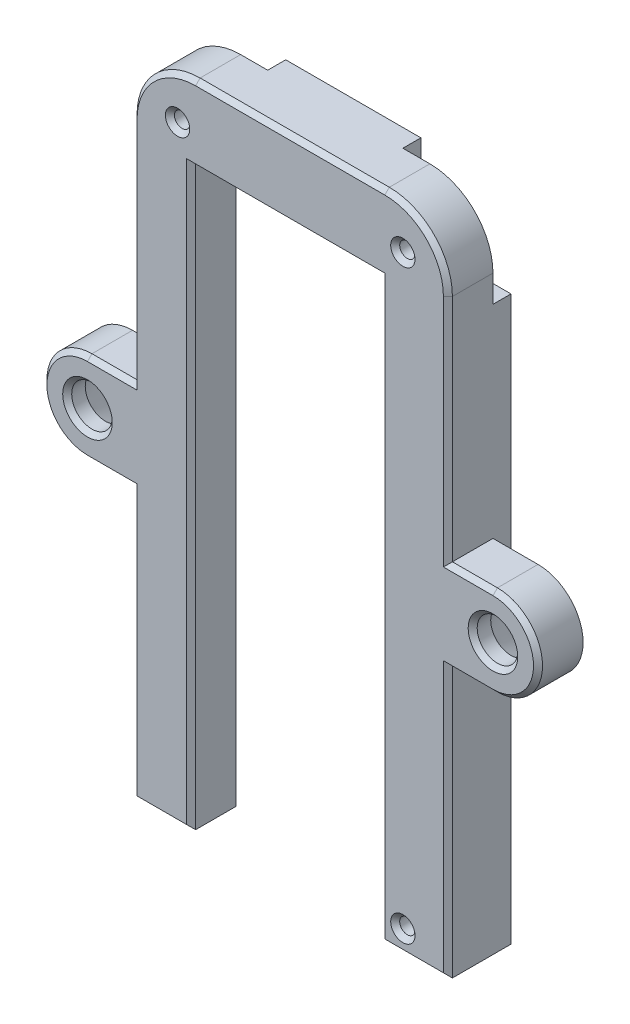
SolidWorks part; units mm, degrees
ref_plane "Front Plane" through (0, 0, 0) normal (0, 0, 1) x (1, 0, 0)
ref_plane "Top Plane" through (0, 0, 0) normal (0, 1, 0) x (1, 0, 0)
ref_plane "Right Plane" through (0, 0, 0) normal (1, 0, 0) x (0, 0, -1)
sketch "Sketch1" plane through (0, 0, 0) normal (0, 0, 1) x (1, 0, 0)
  line L0 (-11, -35) -> (-11, 29)
  line L1 (-15, -35) -> (15, -35) construction
  line L2 (-15, -35) -> (-15, 35) construction
  line L3 (-15, 35) -> (15, 35) construction
  line L4 (15, -35) -> (15, 35) construction
  line L5 (-11, 29) -> (10, 29)
  line L6 (10, 29) -> (10, -35)
  line L7 (-11, -35) -> (-17.5, -35)
  line L8 (-17.5, -35) -> (-17.5, 37.5)
  line L9 (-17.5, 37.5) -> (17.5, 37.5)
  line L10 (17.5, 37.5) -> (17.5, -35)
  line L11 (17.5, -35) -> (10, -35)
  circle A0 centre (-12.5, 32.5) radius 0.85
  circle A1 centre (12.5, 32.5) radius 0.85
  circle A3 centre (12.5, -32.5) radius 0.85
  point P4 (0, 35)
  point P5 (-15, 0)
  point P21 (0, 0)
  point P22 (0, 0)
  point P23 (0, 0)
  point P26 (0, 0)
  point P27 (0, 0)
  point P28 (0, 0)
  point P29 (0, 0)
  dimension "D6" = 1.7
  dimension "D1" = 30
  dimension "D2" = 70
  dimension "D3" = 4
  dimension "D4" = 5
  dimension "D5" = 6
  dimension "D7" = 2.5
  dimension "D8" = 2.5
  dimension "D9" = 2.5
  dimension "D10" = 2.5
  dimension "D11" = 6.5
  dimension "D12" = 7.5
  dimension "D13" = 8.5
  dimension "D16" = 2.5
extrude "Boss-Extrude1" add sketch "Sketch1" along normal blind 5
sketch "Sketch2" plane through (0, 0, 0) normal (0, 0, 1) x (1, 0, 0)
  line L0 (17.5, -35) -> (10, -35) construction
  line L1 (17.5, 37.5) -> (30, 37.5)
  line L2 (17.5, 37.5) -> (17.5, -35)
  line L3 (17.5, -35) -> (15.1, -35)
  line L4 (15.1, 35.1) -> (15.1, -35)
  line L5 (-17.5, 37.5) -> (-30, 37.5)
  line L6 (-17.5, 37.5) -> (-17.5, -35)
  line L7 (-17.5, -35) -> (-15.1, -35)
  line L8 (-15.1, 35.1) -> (-15.1, -35)
  line L9 (30, 37.5) -> (-30, 37.5)
  line L11 (15.1, 35.1) -> (-15.1, 35.1)
  line L12 (15, -35) -> (15, 35) construction
  line L13 (-17.5, -35) -> (-11, -35) construction
  line L15 (-15, -35) -> (-15, 35) construction
  line L16 (-15, 35) -> (15, 35) construction
  dimension "D1" = 0.1
  dimension "D2" = 0.1
  dimension "D3" = 0.1
extrude "Boss-Extrude2" add sketch "Sketch2" against normal blind 2 contours L11 L4 L3 L2 L9 L6 L7 L8 region at (16.6949, 1.25, 0)
sketch "Sketch3" plane through (0, 0, 0) normal (0, 0, 1) x (1, 0, 0)
  line L0 (17.5, 37.5) -> (17.5, -35) construction
  line L1 (22.5, 5) -> (17.5, 5)
  line L3 (22.5, -5) -> (17.5, -5)
  line L4 (17.5, 5) -> (17.5, -5)
  line L5 (-17.5, -35) -> (-17.5, 37.5) construction
  line L6 (-22.5, 5) -> (-17.5, 5)
  line L8 (-22.5, -5) -> (-17.5, -5)
  line L9 (-17.5, 5) -> (-17.5, -5)
  arc A0 (22.5, -5) -> (22.5, 5) centre (22.5, 0) ccw
  arc A1 (-22.5, 5) -> (-22.5, -5) centre (-22.5, 0) ccw
  circle A2 centre (22.5, 0) radius 2.25
  circle A3 centre (-22.5, 0) radius 2.25
  dimension "D1" = 10
  dimension "D2" = 10
  dimension "D3" = 4.5
  dimension "D4" = 4.5
extrude "Boss-Extrude3" add sketch "Sketch3" along normal up to surface (5 mm away) up to face at (-0.25, -0.875, 5)
sketch "Sketch4" plane through (0, 0, 0) normal (0, 0, -1) x (-1, 0, 0)
  circle A0 centre (-22.5, 0) radius 3.5
  circle A1 centre (22.5, 0) radius 3.5
  dimension "D1" = 7
  dimension "D2" = 7
extrude "Cut-Extrude1" cut sketch "Sketch4" against normal blind 3
sketch "Sketch5" plane through (0, 0, 0) normal (0, 0, -1) x (-1, 0, 0)
  line L1 (-7.5, 37.5) -> (-17.5, 37.5)
  line L2 (-7.5, 37.5) -> (-7.5, 27.5)
  line L3 (-7.5, 27.5) -> (-17.5, 27.5)
  line L4 (-17.5, 37.5) -> (-17.5, 27.5)
  line L5 (-7.5, 37.5) -> (-17.5, 27.5) construction
  line L6 (-7.5, 27.5) -> (-17.5, 37.5) construction
  line L7 (7.5, 37.5) -> (17.5, 37.5)
  line L8 (7.5, 37.5) -> (7.5, 27.5)
  line L9 (7.5, 27.5) -> (17.5, 27.5)
  line L10 (17.5, 37.5) -> (17.5, 27.5)
  line L11 (7.5, 37.5) -> (17.5, 27.5) construction
  line L12 (7.5, 27.5) -> (17.5, 37.5) construction
  point P0 (-12.5, 32.5)
  point P5 (12.5, 32.5)
  point P12 (0, 0)
  point P13 (0, 0)
  point P17 (20.8445, 36.306)
extrude "Cut-Extrude2" cut sketch "Sketch5" along normal through all
fillet "Fillet1" radius 7 2 edges at (-17.5, 37.5, 2.5) (17.5, 37.5, 2.5)
chamfer "Chamfer3" distance 0.5 angle 45 26 edges at (-24.75, 0, 5) (20.25, 0, 5) (13.35, 32.5, 5) (-11.65, 32.5, 5) (-17.5, -20, 5) (-20, -5, 5) (-27.5, 0, 5) (-20, 5, 5) (-17.5, 17.75, 5) (0, 37.5, 5) (17.5, 17.75, 5) (20, 5, 5) (27.5, 0, 5) (20, -5, 5) (17.5, -20, 5) (13.75, -35, 5) (-0.5, 29, 5) (-11, -3, 5) (-14.25, -35, 5) (-11.65, 32.5, 0) (13.35, 32.5, 0) (15.4497, 35.4497, 5) (-15.4497, 35.4497, 5) (13.35, -32.5, 5) (13.35, -32.5, 0) (10, -3, 5)
chamfer "Chamfer1" distance 2.5 distance2 1.25 2 edges at (-26, 0, 3) (19, 0, 3) first distance on face at (-26, 0, 3) first distance on face at (19, 0, 3)
